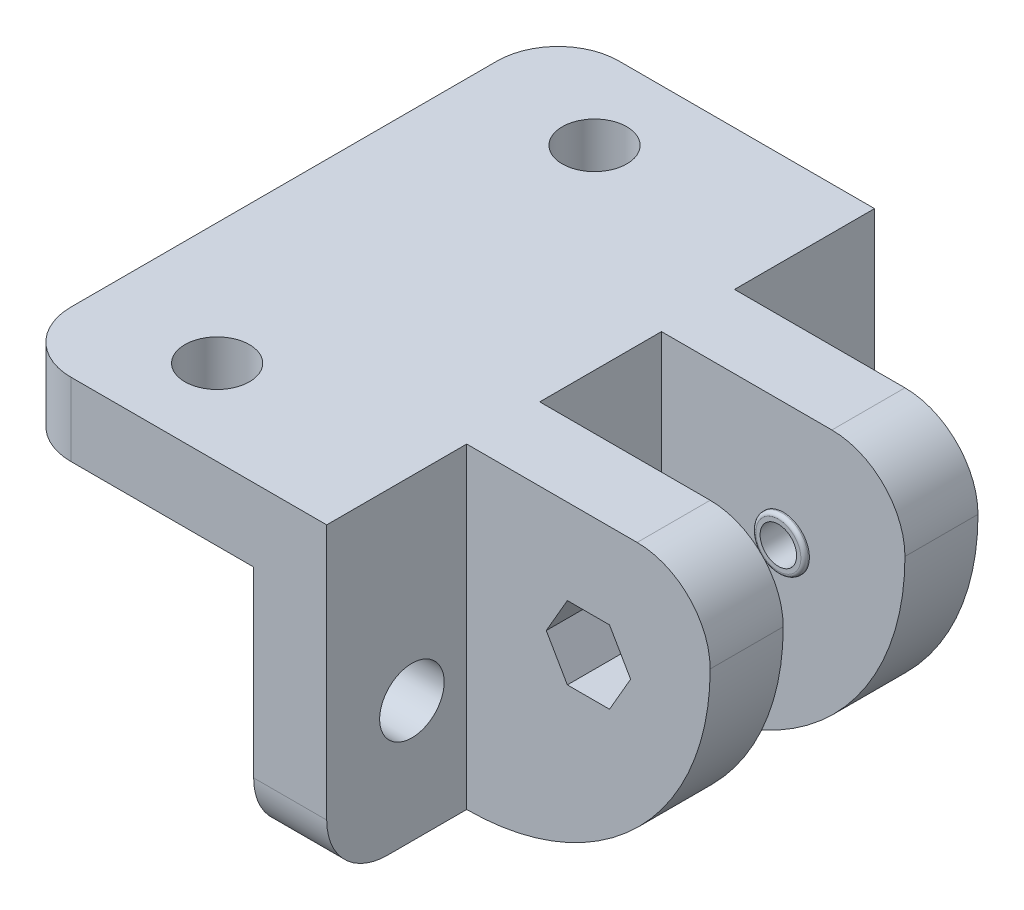
SolidWorks part; units mm, degrees
ref_plane "Front Plane" through (0, 0, 0) normal (0, 0, 1) x (1, 0, 0)
ref_plane "Top Plane" through (0, 0, 0) normal (0, 1, 0) x (1, 0, 0)
ref_plane "Right Plane" through (0, 0, 0) normal (1, 0, 0) x (0, 0, -1)
sketch "Sketch1" plane through (0, 0, 0) normal (1, 0, 0) x (0, 0, -1)
  line L1 (0, 0) -> (45, 0)
  line L2 (0, 0) -> (0, 6)
  line L3 (0, 6) -> (45, 6)
  line L4 (45, 0) -> (45, 6)
  dimension "D1" = 45
  dimension "D2" = 6
extrude "Boss-Extrude1" add sketch "Sketch1" against normal blind 20
sketch "Sketch2" plane through (0, 6, 0) normal (0, 1, 0) x (1, 0, 0)
  line L1 (0, 0) -> (6, 0)
  line L2 (0, 0) -> (0, 45)
  line L3 (0, 45) -> (6, 45)
  line L4 (6, 0) -> (6, 45)
  dimension "D1" = 6
  dimension "D2" = 45
extrude "Boss-Extrude2" add sketch "Sketch2" against normal blind 26
sketch "Sketch3" plane through (0, 6, 0) normal (0, 1, 0) x (1, 0, 0)
  line L0 (-20, 45) -> (-20, 0) construction
  line L1 (-20, 0) -> (6, 0) construction
  line L2 (-20, 45) -> (6, 45) construction
  circle A0 centre (-10, 7) radius 2.65
  circle A1 centre (-10, 38) radius 2.65
  dimension "D3" = 5.3
  dimension "D1" = 10
  dimension "D2" = 7
  dimension "D4" = 7
  dimension "D5" = 10
extrude "Cut-Extrude1" cut sketch "Sketch3" against normal blind 26
sketch "Sketch4" plane through (6, 0, 0) normal (1, 0, 0) x (0, 0, -1)
  line L0 (0, -20) -> (0, 6) construction
  line L1 (0, -20) -> (45, -20) construction
  line L2 (45, -20) -> (45, 6) construction
  circle A0 centre (7, -10) radius 2.65
  circle A1 centre (38, -10) radius 2.65
  dimension "D3" = 5.3
  dimension "D1" = 7
  dimension "D2" = 10
  dimension "D4" = 10
  dimension "D5" = 7
extrude "Cut-Extrude2" cut sketch "Sketch4" against normal blind 26
fillet "Fillet1" radius 5 4 edges at (3, -20, 0) (3, -20, -45) (-20, 3, -45) (-20, 3, 0)
sketch "Sketch5" plane through (6, 0, 0) normal (1, 0, 0) x (0, 0, -1)
  line L0 (0, 6) -> (45, 6) construction
  line L1 (33.5, 6) -> (27.5, 6)
  line L2 (33.5, 6) -> (33.5, -20)
  line L3 (33.5, -20) -> (27.5, -20)
  line L4 (27.5, 6) -> (27.5, -20)
  line L5 (5, -20) -> (40, -20) construction
  line L6 (0, -15) -> (0, 6) construction
  line L7 (11.5, -20) -> (17.5, -20)
  line L8 (11.5, -20) -> (11.5, 6)
  line L9 (11.5, 6) -> (17.5, 6)
  line L10 (17.5, -20) -> (17.5, 6)
  line L11 (45, -15) -> (45, 6) construction
  dimension "D1" = 6
  dimension "D2" = 6
  dimension "D3" = 11.5
  dimension "D4" = 11.5
extrude "Boss-Extrude3" add sketch "Sketch5" along normal blind 20
sketch "Sketch8" plane through (0, 0, -27.5) normal (0, 0, 1) x (1, 0, 0)
  circle A0 centre (16, -4) radius 2.15
  dimension "D1" = 4.3
extrude "Boss-Extrude6" add sketch "Sketch8" along normal blind 0.4
sketch "Sketch7" plane through (0, 0, -17.5) normal (0, 0, -1) x (-1, 0, 0)
  circle A0 centre (-16, -4) radius 2.15
  dimension "D1" = 4.3
extrude "Boss-Extrude5" add sketch "Sketch7" along normal blind 0.4
sketch "Sketch6" plane through (0, 0, -11.5) normal (0, 0, 1) x (1, 0, 0)
  line L1 (26, 6) -> (6, 6) construction
  line L2 (6, 6) -> (6, -20) construction
  circle A0 centre (16, -4) radius 1.5
  dimension "D3" = 3
  dimension "D1" = 10
  dimension "D2" = 10
extrude "Cut-Extrude3" cut sketch "Sketch6" against normal through all
fillet "Fillet2" radius 20 2 edges at (26, -20, -14.5) (26, -20, -30.5)
fillet "Fillet3" radius 6 2 edges at (26, 6, -14.5) (26, 6, -30.5)
fillet "Fillet4" radius 0.3 1 edges at (18.15, -4, -27.1)
fillet "Fillet5" radius 0.3 1 edges at (13.85, -4, -17.9)
sketch "Sketch9" plane through (0, 0, -11.5) normal (0, 0, 1) x (1, 0, 0)
  line L1 (14.2679, -1) -> (12.5359, -4)
  line L2 (12.5359, -4) -> (14.2679, -7)
  line L3 (14.2679, -7) -> (17.7321, -7)
  line L4 (17.7321, -7) -> (19.4641, -4)
  line L5 (19.4641, -4) -> (17.7321, -1)
  line L6 (17.7321, -1) -> (14.2679, -1)
  circle A0 centre (16, -4) radius 3 construction
  dimension "D1" = 6
extrude "Cut-Extrude4" cut sketch "Sketch9" against normal blind 4.5
